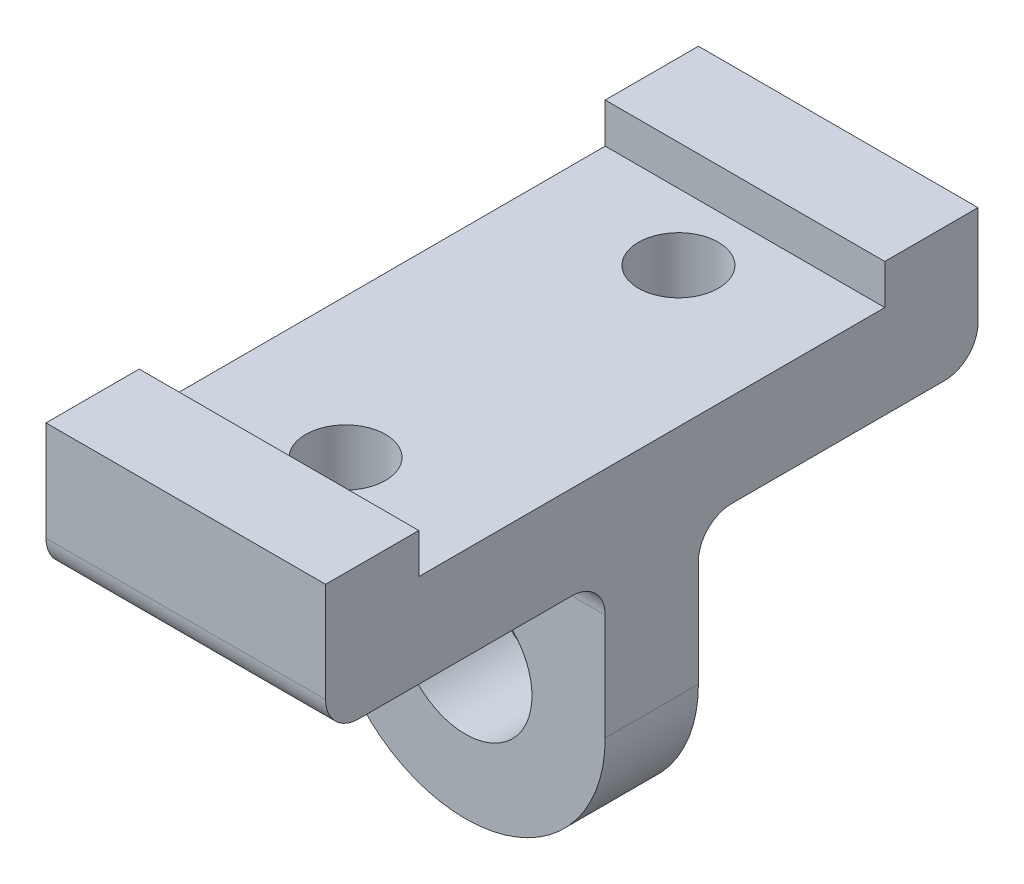
SolidWorks part; units mm, degrees
ref_plane "Front Plane" through (0, 0, 0) normal (0, 0, 1) x (1, 0, 0)
ref_plane "Top Plane" through (0, 0, 0) normal (0, 1, 0) x (1, 0, 0)
ref_plane "Right Plane" through (0, 0, 0) normal (1, 0, 0) x (0, 0, -1)
sketch "Sketch1" plane through (0, 0, 0) normal (0, 1, 0) x (1, 0, 0)
  line L1 (21, -49) -> (-21, -49)
  line L2 (21, -49) -> (21, 49)
  line L3 (21, 49) -> (-21, 49)
  line L4 (-21, -49) -> (-21, 49)
  line L5 (21, -49) -> (-21, 49) construction
  line L6 (21, 49) -> (-21, -49) construction
  point P0 (0, 0)
  dimension "D1" = 98
  dimension "D2" = 42
extrude "Boss-Extrude1" add sketch "Sketch1" along normal blind 20
sketch "Sketch2" plane through (0, 20, 0) normal (0, 1, 0) x (1, 0, 0)
  line L0 (-21, 49) -> (-21, -49) construction
  line L1 (21, -35) -> (-21, -35)
  line L2 (21, -35) -> (21, 35)
  line L3 (21, 35) -> (-21, 35)
  line L4 (-21, -35) -> (-21, 35)
  line L5 (21, -35) -> (-21, 35) construction
  line L6 (21, 35) -> (-21, -35) construction
  line L7 (21, 49) -> (-21, 49) construction
  point P0 (0, 0)
  point P8 (0, 35)
  dimension "D1" = 14
extrude "Cut-Extrude1" cut sketch "Sketch2" against normal blind 6
sketch "Sketch3" plane through (0, 0, 0) normal (0, -1, 0) x (1, 0, 0)
  line L0 (-21, -49) -> (-21, 49) construction
  line L1 (21, -7) -> (-21, -7)
  line L2 (21, -7) -> (21, 7)
  line L3 (21, 7) -> (-21, 7)
  line L4 (-21, -7) -> (-21, 7)
  line L5 (21, -7) -> (-21, 7) construction
  line L6 (21, 7) -> (-21, -7) construction
  point P0 (0, 0)
  dimension "D1" = 14
extrude "Boss-Extrude2" add sketch "Sketch3" along normal blind 42
fillet "Fillet1" radius 21 2 edges at (21, -42, 0) (-21, -42, 0)
sketch "Sketch4" plane through (0, 0, -7) normal (0, 0, -1) x (-1, 0, 0)
  line L0 (-21, -21) -> (21, -21) construction
  circle A0 centre (0, -21) radius 10
  dimension "D1" = 20
extrude "Cut-Extrude2" cut sketch "Sketch4" against normal through all both and the other way through all
sketch "Sketch6" plane through (0, 0, 0) normal (0, 1, 0) x (1, 0, 0)
  line L0 (-21, -7) -> (-21, -49) construction
  line L1 (21, 49) -> (-21, 49) construction
  line L2 (0, 49) -> (0, 7) construction
  line L3 (-21, 7) -> (21, 7) construction
  line L4 (-21, 25) -> (-21, -25)
  line L5 (-21, 25) -> (0, 25) construction
  line L7 (-21, 49) -> (-21, 7) construction
  circle A0 centre (0, 25) radius 6
  point P0 (0, 0)
  point P18 (-10.5, 25)
  dimension "D2" = 12
  dimension "D1" = 24
extrude "Cut-Extrude3" cut sketch "Sketch6" along normal blind 42 contours A0 region at (0, 0, -25)
mirror "Mirror1" about plane through (0, 0, 0) normal (0, 0, 1) of "Cut-Extrude3"
fillet "Fillet2" radius 5 4 edges at (0, 0, 7) (0, 0, -7) (0, 0, 49) (0, 0, -49)
